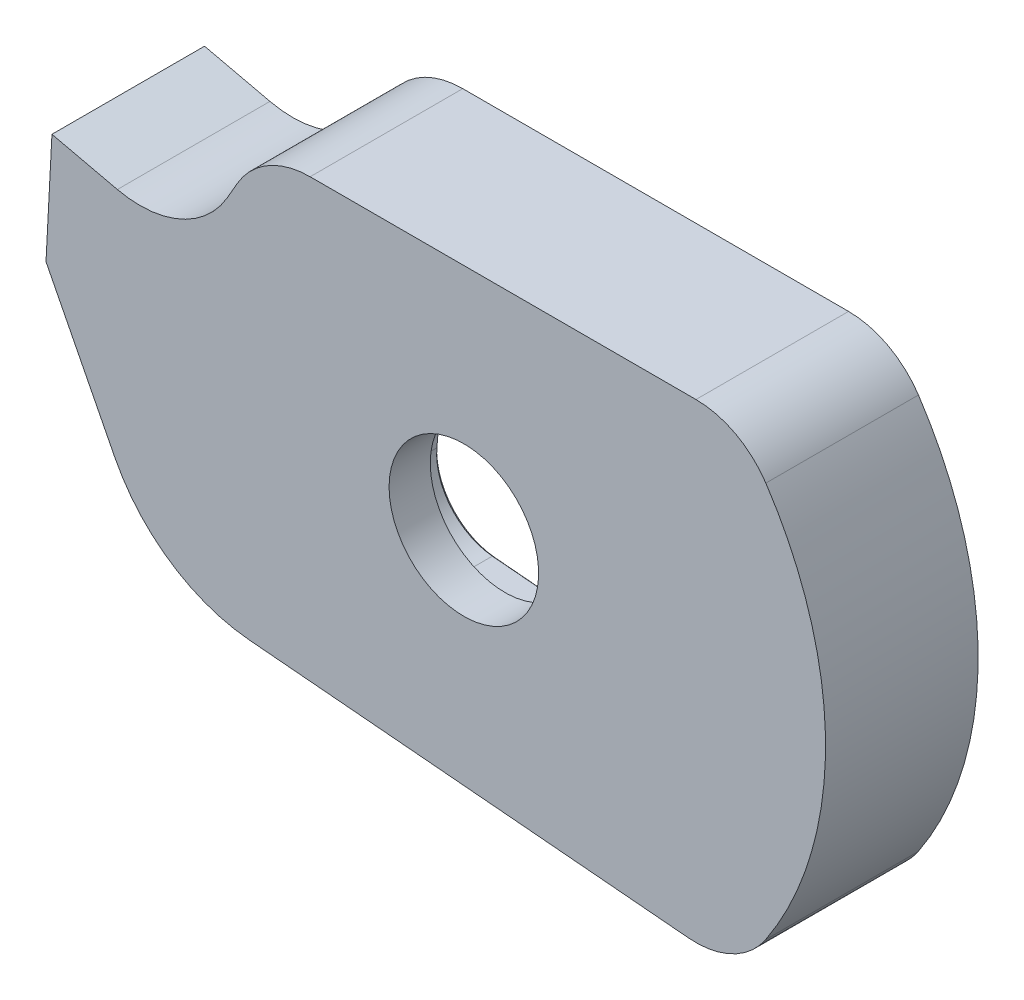
SolidWorks part; units mm, degrees
material "AISI 4340 Aço, normalizado"
ref_plane "Plano frontal" through (0, 0, 0) normal (0, 0, 1) x (1, 0, 0)
ref_plane "Plano superior" through (0, 0, 0) normal (0, 1, 0) x (1, 0, 0)
ref_plane "Plano direito" through (0, 0, 0) normal (1, 0, 0) x (0, 0, -1)
other "Center of Mass"
sketch "Sketch2" plane through (0, 0, 0) normal (0, 0, 1) x (1, 0, 0)
  line L0 (0, 0) -> (-50, 0) construction
  line L1 (-115.1603, 41.8011) -> (-136.5964, 46.75)
  line L2 (0, 0) -> (-142.97, 20.0931) construction
  line L5 (-51.9968, 77) -> (74.4153, 77)
  line L6 (0, 0) -> (0, 41.2714) construction
  line L8 (-75.8125, 63.25) -> (-79.158, 57.4553)
  line L14 (-71.7951, -64.424) -> (71.9488, -77)
  line L19 (-136.5964, 46.75) -> (-138.542, 9.625)
  line L20 (-137.1069, 44.5388) -> (-135.4014, 51.9262) construction
  line L22 (-138.542, 9.625) -> (-116.0069, -34.6028)
  circle A0 centre (0, 0) radius 144.375 construction
  arc A5 (74.4153, 77) -> (97.3123, 64.7308) centre (74.4153, 49.5) cw
  arc A6 (-51.9968, 77) -> (-75.8125, 63.25) centre (-51.9968, 49.5) ccw
  arc A17 (-116.0069, -34.6028) -> (-71.7951, -64.424) centre (-67.0015, -9.6333) ccw
  arc A18 (-115.1603, 41.8011) -> (-79.158, 57.4553) centre (-107.7369, 73.9553) ccw
  arc A20 (97.3123, 64.7308) -> (97.2212, -64.8676) centre (0, 0) cw
  arc A21 (71.9488, -77) -> (97.2212, -64.8676) centre (74.3456, -49.6046) ccw
  point P29 (-144.375, 0)
  point P31 (29.3939, 77)
  point P32 (-67.8739, 77)
  point P33 (97.3123, -64.7308)
  dimension "D1" = 288.75
  dimension "D4" = 27.5
  dimension "D5" = 33
  dimension "D13" = 27.5
  dimension "D11" = 55
  dimension "D10" = 77
  dimension "D2" = 5
  dimension "D3" = 10
  dimension "D7" = 30
  dimension "D8" = 77
  dimension "D12" = 30
  dimension "D9" = 46.75
  dimension "D14" = 37.125
  dimension "D15" = 22
  dimension "D6" = 27.5
  dimension "D16" = 5
  dimension "D17" = 77
extrude "EXTRUSÃO GEOMETRIA" add sketch "Sketch2" along normal blind 50 contours L5 A5 A20 A21 L14 A17 L22 L19 L1 A18 L8 A6
sketch "Esboço3" plane through (0, 0, 0) normal (0, 0, -1) x (-1, 0, 0)
  line L0 (119.5605, -25.8367) -> (117.6529, -4.0323)
  line L1 (125.3653, 6.5829) -> (138.542, 9.625)
  line L2 (138.542, 9.625) -> (116.0069, -34.6028) construction
  line L3 (138.542, 9.625) -> (116.0069, -34.6028)
  line L4 (71.7951, -64.424) -> (-71.9488, -77) construction
  line L5 (115.1603, 41.8011) -> (136.5964, 46.75) construction
  line L6 (31.1551, 77) -> (-22.8799, 20.2266)
  line L7 (51.9968, 77) -> (-74.4153, 77) construction
  line L8 (-28.0452, 17.3392) -> (-116.865, -1.5321)
  line L9 (31.1551, 77) -> (-74.4153, 77)
  arc A0 (71.7951, -64.424) -> (116.0069, -34.6028) centre (67.0015, -9.6333) ccw construction
  arc A1 (117.6529, -4.0323) -> (125.3653, 6.5829) centre (127.6148, -3.1608) cw
  arc A2 (119.5605, -25.8367) -> (116.0069, -34.6028) centre (67.0015, -9.6333) ccw
  arc A3 (-97.3123, 64.7308) -> (-97.2212, -64.8676) centre (0, 0) ccw construction
  arc A4 (-22.8799, 20.2266) -> (-28.0452, 17.3392) centre (-30.1235, 27.1209) cw
  arc A5 (-74.4153, 77) -> (-97.3123, 64.7308) centre (-74.4153, 49.5) ccw construction
  arc A6 (-97.3123, 64.7308) -> (-116.865, -1.5321) centre (0, 0) ccw
  arc A7 (-74.4153, 77) -> (-97.3123, 64.7308) centre (-74.4153, 49.5) ccw
  dimension "D1" = 10
  dimension "D3" = 10
  dimension "D2" = 22
other "Ponto de referência do centro da massa1"
ref_plane "Plano2" through (0, 1.9378, 0) normal (0, -1, 0) x (-1, 0, 0)
ref_plane "Plano3" through (-1.6368, 0, 0) normal (1, 0, 0) x (0, 0, -1)
sketch "Esboço2" plane through (0, 0, 0) normal (0, 0, -1) x (-1, 0, 0)
  line L0 (-8.25, 1.9378) -> (8.25, 1.9378) construction
  line L1 (-38.0236, 53.678) -> (31.7101, 59.7789)
  line L2 (-56.2044, 32.011) -> (-50.1035, -37.7226)
  line L3 (-28.4364, -55.9034) -> (41.2972, -49.8025)
  line L4 (53.3771, 41.5982) -> (59.478, -28.1355)
  line L5 (-57.9475, 51.9349) -> (61.2211, -48.0594) construction
  line L6 (-48.3603, -57.6465) -> (51.6339, 61.5221) construction
  line L7 (1.6368, 8.25) -> (1.6368, -8.25) construction
  line L8 (71.7951, -64.424) -> (-71.9488, -77) construction
  line L10 (2.503, 1.9378) -> (86.0271, 1.9378) construction
  circle A0 centre (1.6368, 1.9378) radius 24.5
  arc A2 (-38.0236, 53.678) -> (-56.2044, 32.011) centre (-36.2805, 33.7542) ccw
  arc A3 (31.7101, 59.7789) -> (53.3771, 41.5982) centre (33.4532, 39.8551) cw
  arc A4 (41.2972, -49.8025) -> (59.478, -28.1355) centre (39.5541, -29.8786) ccw
  arc A5 (-50.1035, -37.7226) -> (-28.4364, -55.9034) centre (-30.1796, -35.9795) ccw
  circle A6 centre (1.6368, 1.9378) radius 42.5
  dimension "D1" = 20
  dimension "D2" = 49
  dimension "D5" = 85
  dimension "D3" = 110
  dimension "D4" = 110
extrude "REBAIXO CAMISA" cut sketch "Esboço2" against normal blind 36.5 contours L1 A3 L4 A4 L3 A5 L2 A2
extrude "FURO EIXO" cut sketch "Esboço2<3>" against normal through all contours A0
sketch "Esboço2<3>" plane through (0, 0, 0) normal (0, 0, -1) x (-1, 0, 0) same geometry as "Esboço2"
chamfer "CHANFRO CAMISA" distance 1 angle 45 8 edges at (-6.4304, -52.8529, 0) (43.0353, -51.3004, 0) (-54.875, -42.7343, 0) (53.1539, -2.8558, 0) (-56.4275, 6.7314, 0) (51.6013, 46.6099, 0) (-46.3089, 55.1759, 0) (3.1568, 56.7285, 0)
sketch "REF. POLIA" plane through (0, 0, 0) normal (0, 0, -1) x (-1, 0, 0)
  circle A0 centre (1.6368, 1.9378) radius 75
  circle A1 centre (1.6368, 1.9378) radius 24.5 construction
  dimension "D1" = 150
equation "\"escala\" = 1                                            'projeto - escala geral"
equation "\"escala_disco-arma\"= 2.75                               'disco arma - escala geometria disco arma"
equation "\"rolamento_D-ext\"= 85                                   'rolamento arma - diametro externo"
equation "\"rolamento_d-int\"= 45                                   'rolamento arma - diametro interno"
equation "\"rolamento_b-esp\"= 23                                   'rolamento arma - espessura"
equation "\"arma_rebaixo-camisa_b\"= \"rolamento_b-esp\" + (\"arma-espessura\"-\"rolamento_b-esp\")/2        'disco arma - profundidade rebaixo camisa"
equation "\"arma-espessura\"= 50                                    'disco arma - espessura disco arma"
equation "\"D1@EXTRUSÃO GEOMETRIA\" = \"arma-espessura\""
equation "\"eixo_diam\"= \"rolamento_d-int\"                          'eixo arma - diametro"
equation "\"D2@Esboço2\" = \"eixo_diam\" + \"arma_eixo-furo_folga\""
equation "\"camisa_largura\"=110                                    'camisa arma - tamanho do lado"
equation "\"D3@Esboço2\"=\"camisa_largura\""
equation "\"camisa_raio\"=15                                        'camisa arma - raio canto interno"
equation "\"arma_rebaixo-camisa_raio\" = 5 + \"camisa_raio\"          'raio do rebaixo da camisa da arma "
equation "\"D1@Esboço2\"=\"arma_rebaixo-camisa_raio\""
equation "\"arma_alivio_raio\"= 12 * \"escala_disco-arma\""
equation "\"arma_diam_max\"= 105 * \"escala_disco-arma\""
equation "\"D1@Sketch2\" = \"arma_diam_max\""
equation "\"arma_arestas_raio\"= 10 * \"escala_disco-arma\""
equation "\"D4@Sketch2\" = \"arma_arestas_raio\""
equation "\"arma_altura_superior-centro\"= 28 * \"escala_disco-arma\""
equation "\"D10@Sketch2\" = \"arma_altura_superior-centro\""
equation "\"arma_dente_raio\"= 12 * \"escala_disco-arma\""
equation "\"D5@Sketch2\" = \"arma_dente_raio\""
equation "\"arma_altura_dente-centro\"= 17 * \"escala_disco-arma\""
equation "\"D9@Sketch2\"=\"arma_altura_dente-centro\""
equation "\"arma_dente_altura\"= 13.5 * \"escala_disco-arma\""
equation "\"arma_alivio-dente_raio\"= 20 * \"escala_disco-arma\""
equation "\"arma_traseira_offset\"= 10 * \"escala_disco-arma\""
equation "\"arma_centralizacao_offset\"= 8 * \"escala_disco-arma\""
equation "\"arma_eixo-furo_folga\" = 4                              'arma - folga entre furo arma e eixo"
equation "\"D1@REBAIXO CAMISA\" = \"arma_rebaixo-camisa_b\""
equation "\"D6@Sketch2\"=\"arma_traseira_offset\""
equation "\"D11@Sketch2\"=\"arma_alivio-dente_raio\""
equation "\"D4@Esboço2\"=\"camisa_largura\""
equation "\"D14@Sketch2\"=\"arma_dente_altura\""
equation "\"arma_altura_inferior-centro\"= 28 * \"escala_disco-arma\""
equation "\"D17@Sketch2\"=\"arma_altura_inferior-centro\""
equation "\"D13@Sketch2\"=\"arma_arestas_raio\""
equation "\"D5@Esboço2\"=\"rolamento_D-ext\""
equation "\"polia_diam_eff\" = 150 "
equation "\"D1@REF. POLIA\" = \"polia_diam_eff\""
equation "\"arma_dente_comprimento\"=22"
equation "\"D15@Sketch2\"=\"arma_dente_comprimento\""
